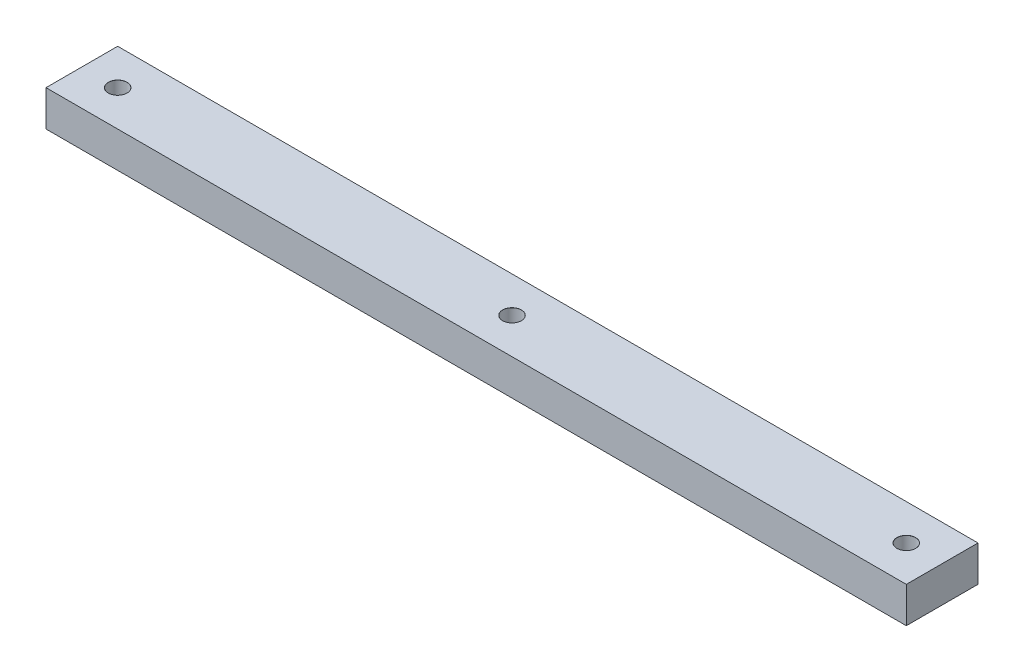
SolidWorks part; units mm, degrees
ref_plane "Front Plane" through (0, 0, 0) normal (0, 0, 1) x (1, 0, 0)
ref_plane "Top Plane" through (0, 0, 0) normal (0, 1, 0) x (1, 0, 0)
ref_plane "Right Plane" through (0, 0, 0) normal (1, 0, 0) x (0, 0, -1)
sketch "Sketch1" plane through (0, 0, 0) normal (0, 1, 0) x (1, 0, 0)
  line L0 (0, 0) -> (0, 37.5156) construction
  line L1 (152.4, -12.7) -> (-152.4, -12.7)
  line L2 (152.4, -12.7) -> (152.4, 12.7)
  line L3 (152.4, 12.7) -> (-152.4, 12.7)
  line L4 (-152.4, -12.7) -> (-152.4, 12.7)
  line L5 (152.4, -12.7) -> (-152.4, 12.7) construction
  line L6 (152.4, 12.7) -> (-152.4, -12.7) construction
  point P0 (0, 0)
  point P6 (-139.7, 0)
  point P8 (-152.4, 0)
  point P10 (139.7, 0)
  dimension "D1" = 304.8
  dimension "D2" = 25.4
  dimension "D3" = 12.7
extrude "Boss-Extrude1" add sketch "Sketch1" along normal blind 12.7
hole_wizard "M6 Clearance Hole1" positions "3DSketch1" profile "Sketch2" hole size "M6" standard "ANSI Metric" end condition through all
sketch3d "3DSketch1"
  point P0 (0, 12.7, 0)
  point P4 (-139.7, 12.7, 0)
  point P6 (139.7, 12.7, 0)
sketch "Sketch2" plane through (0, 12.7, 0) normal (1, 0, 0) x (0, 0, 1)
  line L0 (0, 0) -> (0, 12.7)
  line L1 (0, 12.7) -> (3.3, 12.7)
  line L2 (3.3, 12.7) -> (3.3, 0.025)
  line L3 (3.3, 0.025) -> (3.325, 0)
  line L5 (3.325, 0) -> (0, 0)
  line L6 (-3.3, 0.025) -> (-3.325, 0) construction
  line L11 (0, -6.35) -> (0, 107.95) construction
  dimension "Thru Hole Dia." = 6.6
  dimension "Thru Hole Depth" = 12.7
  dimension "Near C'Sink Dia." = 6.65
  dimension "Near C'Sink Angle" = 90
equation "\"Rover_Length\"= 25in"
equation "\"Rover_Width\"= 18in"
equation "\"Rover_Height\"= 12in"
equation "\"Chassis_Wheelbase\"= 28in"
equation "\"Chassis_WheelDiam\"= 171mm"
equation "\"Chassis_ArmDiamWidth\"= 0.75in"
equation "\"Chassis_ArmAngle\"= 135deg"
equation "\"Chassis_ArmHeight\"= 8in"
equation "\"Chassis_HubMountOD\"= 3in"
equation "\"Chassis_WheelBoltHole\"= 36mm"
equation "\"Chassis_WheelBoltNum\"= 4"
equation "\"Chassis_DiffBarLength\"= 12in"
equation "\"Chassis_DiffBarWidth\"= 1in"
equation "\"Chassis_DiffBarHeight\"= 0.5in"
equation "\"Chassis_DiffLinkage_Length\"= 2.5in"
equation "\"Chassis_MountBracketThickness\"= 0.125in"
equation "\"Chassis_MountBracketWidth\"= 3in"
equation "\"Chassis_MountBacketOverlap\"= 0.5in"
equation "\"Chassis_ArmShaftDiam\"= 0.75in"
equation "\"Chassis_ArmHoleSpacing\"= 1.25in"
equation "\"D1@Sketch1\"=\"Chassis_DiffBarLength\""
equation "\"D2@Sketch1\"=\"Chassis_DiffBarWidth\""
equation "\"D1@Boss-Extrude1\"=\"Chassis_DiffBarHeight\""
